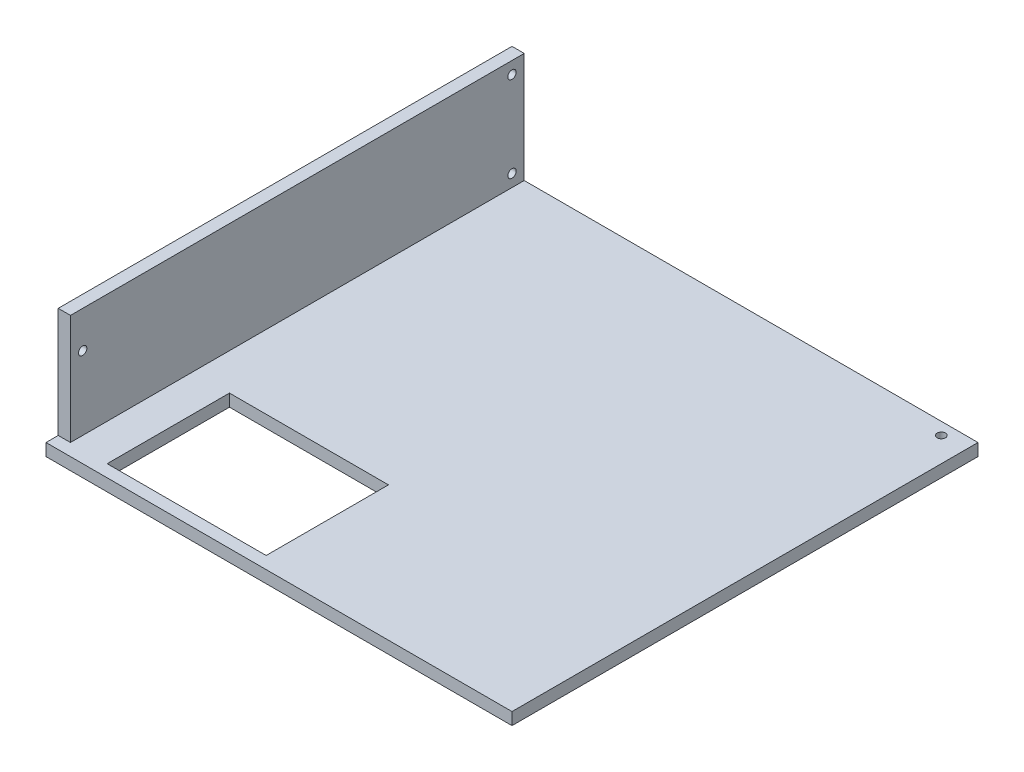
SolidWorks part; units mm, degrees
ref_plane "Front Plane" through (0, 0, 0) normal (0, 0, 1) x (1, 0, 0)
ref_plane "Top Plane" through (0, 0, 0) normal (0, 1, 0) x (1, 0, 0)
ref_plane "Right Plane" through (0, 0, 0) normal (1, 0, 0) x (0, 0, -1)
sketch "Sketch1" plane through (0, 0, 0) normal (0, 1, 0) x (1, 0, 0)
  line L1 (-95.25, 95.25) -> (95.25, 95.25)
  line L2 (-95.25, 95.25) -> (-95.25, -95.25)
  line L3 (-95.25, -95.25) -> (95.25, -95.25)
  line L4 (95.25, 95.25) -> (95.25, -95.25)
  line L5 (-95.25, 95.25) -> (95.25, -95.25) construction
  line L6 (-95.25, -95.25) -> (95.25, 95.25) construction
  point P0 (0, 0)
  dimension "D1" = 190.5
  dimension "D2" = 190.5
extrude "Boss-Extrude1" add sketch "Sketch1" along normal blind 5
sketch "Sketch2" plane through (0, 5, 0) normal (0, 1, 0) x (1, 0, 0)
  line L0 (-95.25, -95.25) -> (95.25, -95.25) construction
  line L1 (-95.25, 95.25) -> (-90.25, 95.25)
  line L2 (-95.25, 95.25) -> (-95.25, -95.25)
  line L3 (-95.25, -95.25) -> (-90.25, -95.25)
  line L4 (-90.25, 95.25) -> (-90.25, -95.25)
  dimension "D1" = 5
extrude "Boss-Extrude2" add sketch "Sketch2" along normal blind 45
sketch "Sketch5" plane through (-95.25, 0, 0) normal (-1, 0, 0) x (0, 0, 1)
  line L0 (-95.25, 0) -> (95.25, 0) construction
  line L1 (95.25, 50) -> (90.25, 50)
  line L2 (95.25, 50) -> (95.25, 5)
  line L3 (95.25, 5) -> (90.25, 5)
  line L4 (90.25, 50) -> (90.25, 5)
  dimension "D1" = 5
  dimension "D2" = 5
extrude "Cut-Extrude1" cut sketch "Sketch5" against normal up to surface (5 mm away) up to face at (-90.25, 27.5, 0)
sketch "Sketch6" plane through (0, 0, 0) normal (0, -1, 0) x (1, 0, 0)
  line L1 (-10.25, 90.25) -> (-75.25, 90.25)
  line L2 (-10.25, 90.25) -> (-10.25, 40.25)
  line L3 (-10.25, 40.25) -> (-75.25, 40.25)
  line L4 (-75.25, 90.25) -> (-75.25, 40.25)
  line L6 (-95.25, -95.25) -> (-95.25, 95.25) construction
  line L7 (-95.25, 95.25) -> (95.25, 95.25) construction
  dimension "D1" = 50
  dimension "D2" = 65
  dimension "D3" = 20
  dimension "D4" = 5
extrude "Cut-Extrude2" cut sketch "Sketch6" against normal up to surface (5 mm away) up to face at (-30.0833, 5, 30.0833)
sketch "Sketch7" plane through (-95.25, 0, 0) normal (-1, 0, 0) x (0, 0, 1)
  line L0 (90.25, 50) -> (90.25, 5) construction
  line L1 (-95.25, 50) -> (90.25, 50) construction
  line L2 (-95.25, 0) -> (95.25, 0) construction
  line L3 (-95.25, 50) -> (-95.25, 0) construction
  circle A0 centre (85.25, 35) radius 1.7
  circle A1 centre (-90.25, 45) radius 1.7
  circle A2 centre (-90.25, 10) radius 1.7
  point P10 (0, 0)
  dimension "D1" = 3.4
  dimension "D4" = 10
  dimension "D2" = 5
  dimension "D3" = 15
  dimension "D5" = 5
  dimension "D6" = 5
extrude "Cut-Extrude3" cut sketch "Sketch7" against normal up to surface (5 mm away) up to face at (-90.25, 27.5, -2.5)
sketch "Sketch9" plane through (0, 0, 0) normal (0, -1, 0) x (1, 0, 0)
  line L0 (95.25, -95.25) -> (-95.25, -95.25) construction
  line L1 (95.25, 95.25) -> (95.25, -95.25) construction
  circle A0 centre (85.25, -90.25) radius 1.7
  dimension "D3" = 3.4
  dimension "D1" = 5
  dimension "D2" = 10
extrude "Cut-Extrude4" cut sketch "Sketch9" against normal up to surface (5 mm away) up to face at (-42.75, 5, 65.25)
sketch "Sketch10" plane through (0, 0, 0) normal (0, -1, 0) x (1, 0, 0)
  circle A0 centre (85.25, -90.25) radius 2.2
  dimension "D1" = 4.4
extrude "Cut-Extrude5" cut sketch "Sketch10" against normal blind 2
sketch "Sketch11" plane through (-95.25, 0, 0) normal (-1, 0, 0) x (0, 0, 1)
  circle A0 centre (-90.25, 10) radius 2.2
  circle A2 centre (85.25, 35) radius 2.2
  circle A4 centre (-90.25, 45) radius 2.2
  dimension "D1" = 4.4
  dimension "D2" = 4.4
extrude "Cut-Extrude6" cut sketch "Sketch11" against normal blind 2
